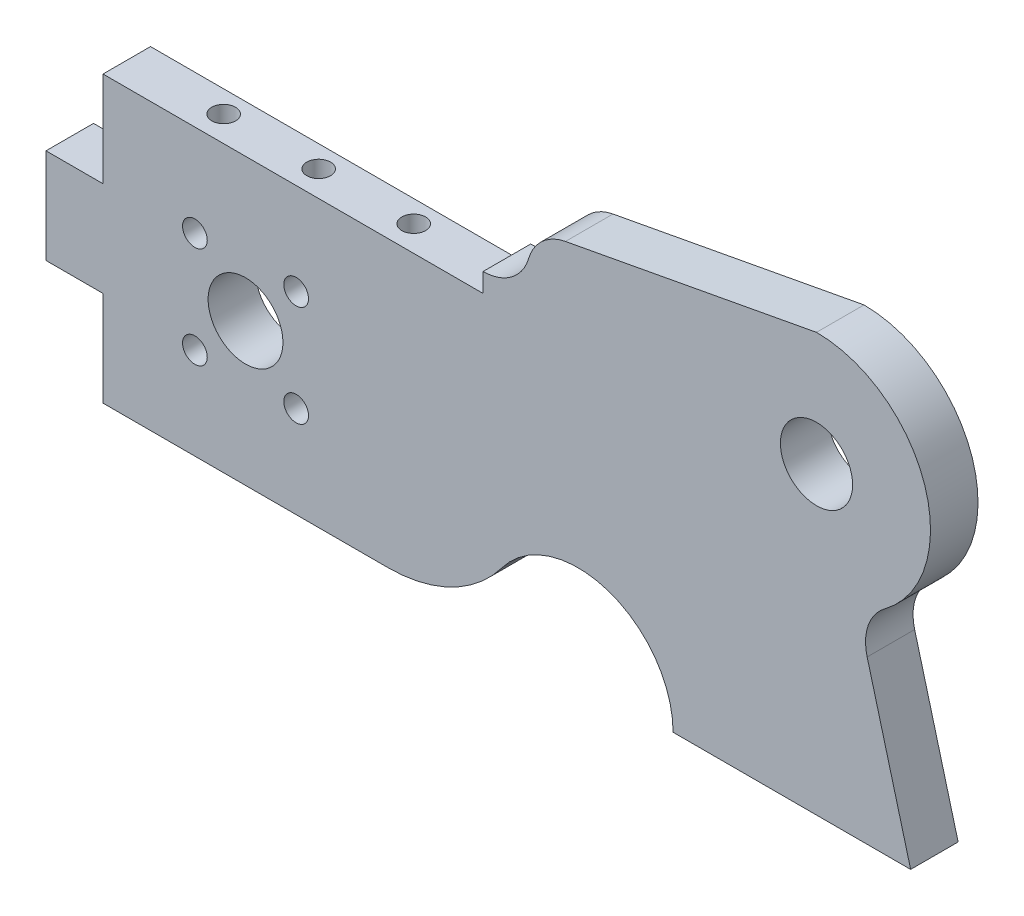
SolidWorks part; units mm, degrees
ref_plane "Front Plane" through (0, 0, 0) normal (0, 0, 1) x (1, 0, 0)
ref_plane "Top Plane" through (0, 0, 0) normal (0, 1, 0) x (1, 0, 0)
ref_plane "Right Plane" through (0, 0, 0) normal (1, 0, 0) x (0, 0, -1)
sketch "Sketch1" plane through (0, 0, 0) normal (0, 0, 1) x (1, 0, 0)
  line L0 (0, 0) -> (107.95, 0)
  line L3 (0, 38.1) -> (0, 25.4)
  line L4 (95.3675, 55.88) -> (0, 38.1)
  line L5 (0, 19.05) -> (100.2273, 19.05) construction
  line L6 (19.05, 19.05) -> (19.05, 28.62) construction
  line L7 (19.05, 19.05) -> (25.817, 25.817) construction
  line L8 (107.95, 0) -> (100.9363, 26.1756)
  line L10 (0, 12.7) -> (0, 0)
  line L11 (0, 25.4) -> (-7.62, 25.4)
  line L13 (0, 12.7) -> (-7.62, 12.7)
  line L14 (-7.62, 25.4) -> (-7.62, 12.7)
  line L15 (100.9363, 26.1756) -> (100.8688, 26.4276)
  arc A0 (100.8688, 26.4276) -> (95.3675, 55.88) centre (95.3675, 40.64) ccw
  circle A1 centre (95.3675, 40.64) radius 4.826
  circle A2 centre (19.05, 19.05) radius 9.57 construction
  circle A3 centre (25.817, 25.817) radius 1.651
  circle A4 centre (25.817, 12.283) radius 1.651
  circle A5 centre (12.283, 12.283) radius 1.651
  circle A6 centre (12.283, 25.817) radius 1.651
  point P26 (19.05, 19.05)
  dimension "D1" = 9.652
  dimension "D5" = 15.24
  dimension "D4" = 19.14
  dimension "D7" = 3.302
  dimension "D11" = 97.0107
  dimension "D2" = 38.1
  dimension "D3" = 40.64
  dimension "D6" = 107.95
  dimension "D8" = 45
  dimension "D9" = 4
  dimension "D10" = 19.05
  dimension "D12" = 75
  dimension "D14" = 12.7
  dimension "D15" = 12.7
  dimension "D16" = 7.62
extrude "Boss-Extrude1" add sketch "Sketch1" along normal blind 6.35
sketch "Sketch2" plane through (0, 0, 6.35) normal (0, 0, 1) x (1, 0, 0)
  circle A0 centre (95.3675, 40.64) radius 38.1 construction
sketch "Sketch3" plane through (0, 0, 0) normal (-1, 0, 0) x (0, 0, 1)
  line L0 (0, 38.1) -> (6.35, 25.4) construction
  line L1 (6.35, 12.7) -> (0, 0) construction
  circle A0 centre (3.175, 31.75) radius 1.5875
  circle A1 centre (3.175, 6.35) radius 1.5875
  dimension "D1" = 3.175
  dimension "D2" = 3.175
extrude "Cut-Extrude1" cut sketch "Sketch3" against normal blind 6.35
sketch "Sketch6" plane through (0, 0, 6.35) normal (0, 0, 1) x (1, 0, 0)
  line L0 (0, 0) -> (107.95, 0) construction
  line L1 (50.8, 0) -> (76.2, 0)
  arc A0 (76.2, 0) -> (50.8, 0) centre (63.5, 0) ccw
  dimension "D1" = 25.4
  dimension "D2" = 31.75
extrude "Cut-Extrude2" cut sketch "Sketch6" against normal blind 6.35
sketch "Sketch7" plane through (0, 0, 6.35) normal (0, 0, 1) x (1, 0, 0)
  line L0 (12.283, 25.817) -> (25.817, 12.283) construction
  line L1 (12.283, 12.283) -> (25.817, 25.817) construction
  circle A0 centre (19.05, 19.05) radius 5
  dimension "D1" = 10
extrude "Cut-Extrude3" cut sketch "Sketch7" against normal through all
fillet "Fillet1" radius 6.35 1 edges at (100.8688, 26.4276, 3.175)
sketch "Sketch8" plane through (0, 0, 6.35) normal (0, 0, 1) x (1, 0, 0)
  line L1 (0, 38.1) -> (50.8, 38.1)
  line L2 (0, 38.1) -> (0, 50.8)
  line L3 (0, 50.8) -> (50.8, 50.8)
  line L4 (50.8, 38.1) -> (50.8, 50.8)
  dimension "D1" = 50.8
  dimension "D2" = 12.7
extrude "Cut-Extrude4" cut sketch "Sketch8" against normal blind 50.8
sketch "Sketch9" plane through (0, 0, 6.35) normal (0, 0, 1) x (1, 0, 0)
  line L3 (50.8, 40.64) -> (57.15, 40.64)
  line L5 (57.15, 40.64) -> (50.8, 40.64)
  line L6 (57.15, 40.64) -> (57.15, 50.8)
  line L7 (57.15, 50.8) -> (50.8, 50.8)
  line L8 (50.8, 40.64) -> (50.8, 50.8)
  line L9 (0, 38.1) -> (50.8, 38.1) construction
  line M8 (50.8, 47.571) -> (50.8, 38.1)
  line M21 (95.3675, 55.88) -> (50.8, 47.571)
  dimension "D1" = 10.16
  dimension "D2" = 2.54
  dimension "D3" = 6.35
extrude "Cut-Extrude5" cut sketch "Sketch9" against normal blind 19.304 contours L3 L6 M21 M8 region at (54.0583, 44.4092, 6.35)
fillet "Fillet6" radius 6.35 1 edges at (57.15, 40.64, 3.175)
fillet "Fillet7" radius 6.35 1 edges at (57.15, 48.7549, 3.175)
fillet "Fillet8" radius 19.05 1 edges at (50.8, 0, 3.175)
sketch "Sketch10" plane through (0, 0, 0) normal (0, -1, 0) x (1, 0, 0)
  line L0 (76.2, 6.35) -> (107.95, 6.35) construction
  line L1 (0, 6.35) -> (0, 0) construction
  line L2 (0, 6.35) -> (38.1, 6.35) construction
  line L3 (107.95, 6.35) -> (107.95, 0) construction
  line L4 (76.2, 0) -> (76.2, 6.35) construction
  circle A0 centre (97.79, 3.175) radius 1.5875
  circle A1 centre (86.36, 3.175) radius 1.5875
  circle A2 centre (31.75, 3.175) radius 1.5875
  circle A3 centre (12.7, 3.175) radius 1.5875
  dimension "D1" = 3.175
  dimension "D2" = 3.175
  dimension "D3" = 3.175
  dimension "D4" = 3.175
  dimension "D5" = 12.7
  dimension "D6" = 19.05
  dimension "D7" = 10.16
  dimension "D8" = 10.16
  dimension "D9" = 11.43
  dimension "D10" = 3.175
  dimension "D11" = 3.175
extrude "Cut-Extrude6" cut sketch "Sketch10" against normal blind 6.35
sketch "Sketch11" plane through (0, 38.1, 0) normal (0, 1, 0) x (1, 0, 0)
  line L0 (0, -6.35) -> (0, 0) construction
  line L1 (50.8, 0) -> (50.8, -6.35) construction
  line L2 (0, -6.35) -> (50.8, -6.35) construction
  circle A0 centre (12.7, -2.9224) radius 1.5875
  circle A1 centre (25.4, -2.9224) radius 1.5875
  circle A2 centre (38.1, -2.9224) radius 1.5875
  dimension "D1" = 3.175
  dimension "D2" = 3.175
  dimension "D3" = 3.175
  dimension "D4" = 12.7
  dimension "D5" = 12.7
  dimension "D6" = 12.7
  dimension "D7" = 12.7
  dimension "D8" = 3.4276
extrude "Cut-Extrude7" cut sketch "Sketch11" against normal blind 6.35
